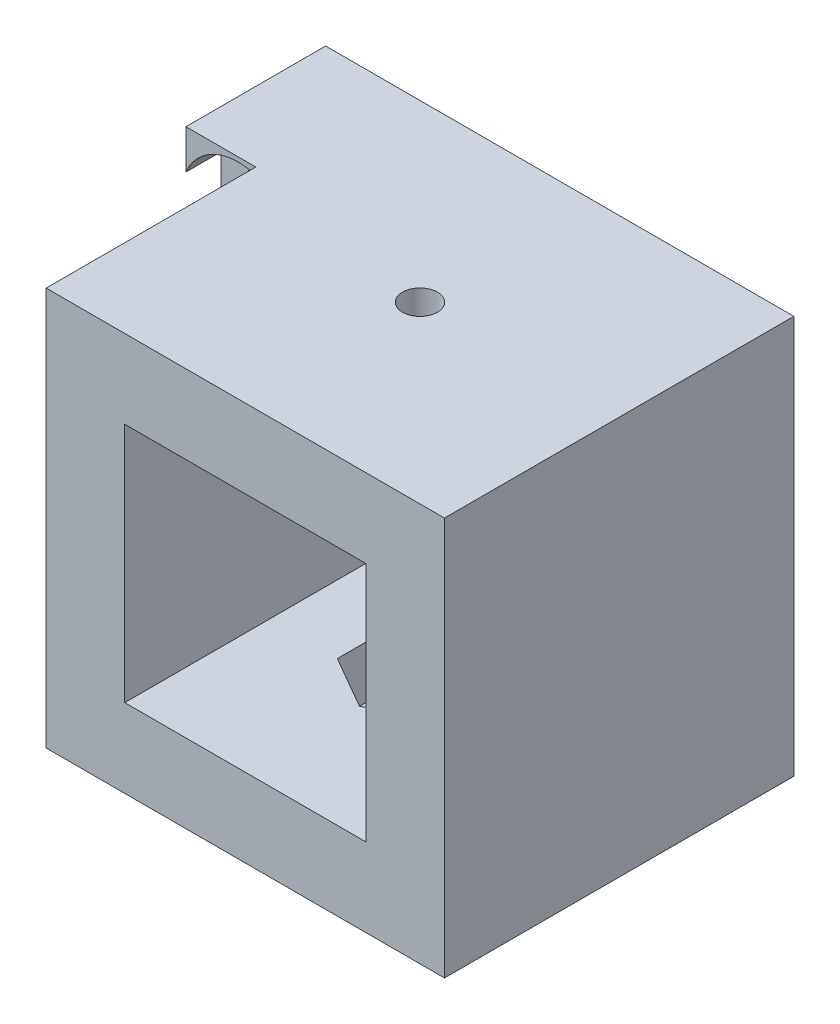
SolidWorks part; units mm, degrees
ref_plane "Alzado" through (0, 0, 0) normal (0, 0, 1) x (1, 0, 0)
ref_plane "Planta" through (0, 0, 0) normal (0, 1, 0) x (1, 0, 0)
ref_plane "Vista lateral" through (0, 0, 0) normal (1, 0, 0) x (0, 0, -1)
sketch "Croquis1" plane through (0, 0, 0) normal (0, 0, 1) x (1, 0, 0)
  line L0 (-11.4, -11.4) -> (-11.4, 11.4)
  line L1 (-6.9, -6.9) -> (6.9, -6.9)
  line L2 (-6.9, -6.9) -> (-6.9, 6.9)
  line L3 (-6.9, 6.9) -> (6.9, 6.9)
  line L4 (6.9, -6.9) -> (6.9, 6.9)
  line L5 (-6.9, -6.9) -> (6.9, 6.9) construction
  line L6 (-6.9, 6.9) -> (6.9, -6.9) construction
  line L7 (-11.4, 11.4) -> (11.4, 11.4)
  line L8 (11.4, -11.4) -> (11.4, 11.4)
  line L9 (-11.4, -11.4) -> (11.4, -11.4)
  point P0 (0, 0)
  dimension "D1" = 13.8
  dimension "D2" = 13.8
  dimension "D3" = 4.5
extrude "Saliente-Extruir1" add sketch "Croquis1" along normal mid plane 20
sketch "Croquis2" plane through (0, -6.9, 0) normal (0, 1, 0) x (1, 0, 0)
  line L1 (3, -1.7321) -> (3, 1.7321)
  line L2 (3, 1.7321) -> (0, 3.4641)
  line L3 (0, 3.4641) -> (-3, 1.7321)
  line L4 (-3, 1.7321) -> (-3, -1.7321)
  line L5 (-3, -1.7321) -> (0, -3.4641)
  line L6 (0, -3.4641) -> (3, -1.7321)
  circle A0 centre (0, 0) radius 3 construction
  dimension "D1" = 6
extrude "Cortar-Extruir1" cut sketch "Croquis2" against normal blind 3
sketch "Croquis3" plane through (0, -9.9, 0) normal (0, 1, 0) x (1, 0, 0)
  circle A0 centre (0, 0) radius 1.75
  dimension "D1" = 3.5
extrude "Cortar-Extruir2" cut sketch "Croquis3" against normal blind 3
sketch "Croquis4" plane through (0, 0, -10) normal (0, 0, -1) x (-1, 0, 0)
  line L0 (12.4, 11.4) -> (12.4, 4.4) construction
  line L1 (11.4, 11.4) -> (15.4, 11.4)
  line L2 (11.4, 11.4) -> (11.4, 4.4)
  line L3 (11.4, 4.4) -> (15.4, 4.4)
  line L4 (-11.4, -11.4) -> (11.4, -11.4)
  line L5 (11.4, -11.4) -> (11.4, 11.4)
  line L6 (11.4, 11.4) -> (-11.4, 11.4)
  line L7 (-11.4, 11.4) -> (-11.4, -11.4)
  line L8 (-11.4, -11.4) -> (11.4, -11.4)
  line L9 (11.4, -11.4) -> (11.4, 11.4)
  line L10 (11.4, 11.4) -> (-11.4, 11.4)
  line L11 (-11.4, 11.4) -> (-11.4, -11.4)
  line L12 (15.4, 11.4) -> (15.4, 4.4)
  circle A0 centre (12.4, 7.9) radius 1.75
  line M12 (11.4, -11.4) -> (11.4, 11.4)
  dimension "D2" = 3.5
  dimension "D3" = 4
  dimension "D4" = 1
  dimension "D5" = 7
  dimension "D1" = 0
extrude "Saliente-Extruir3" add sketch "Croquis4" against normal blind 8 contours L1 L0 A0 L3 L12 | L0 A0 L3 M12 | L0 L1 A0 M12 region at (-13.9, 11.3238, -10) region at (-11.8862, 10.4724, -10) region at (-11.8862, 5.3276, -10)
sketch "Croquis8" plane through (0, 0, -10) normal (0, 0, -1) x (-1, 0, 0)
  circle A0 centre (12.4, 7.9) radius 1.75
extrude "Cortar-Extruir3" cut sketch "Croquis8" against normal blind 4
hole_wizard "Refrentado para tornillo con cabeza plana de M31" positions "Croquis3D2" profile "Croquis9" counterbore size "M3" standard "ISO" end condition through all
sketch3d "Croquis3D2"
  line L0 (-12.4, 7.9, -6) -> (-12.4, 7.9, -10) construction
  point P0 (-12.4, 7.9, -2)
sketch "Croquis9" plane through (-12.4, 7.9, -2) normal (1, 0, 0) x (0, -1, 0)
  line L0 (0, 0) -> (0, 8)
  line L1 (0, 8) -> (1.8, 8)
  line L3 (1.8, 8) -> (1.8, 2)
  line L4 (1.8, 2) -> (3.25, 2)
  line L5 (3.25, 2) -> (3.25, 0)
  line L7 (3.25, 0) -> (0, 0)
  line L11 (0, -6.35) -> (0, 107.95) construction
  dimension "Diámetro de taladro hasta el siguiente" = 3.6
  dimension "Profundidad de taladro hasta el siguiente" = 8
  dimension "Diámetro de refrentado" = 6.5
  dimension "Profundidad de refrentado" = 2
sketch "Croquis11" plane through (0, 0, -2) normal (0, 0, 1) x (1, 0, 0)
  line L0 (-15.4, 9.15) -> (-15.4, 6.65)
  arc A0 (-15.4, 6.65) -> (-15.4, 9.15) centre (-12.4, 7.9) ccw construction
  arc A1 (-15.4, 6.65) -> (-15.4, 9.15) centre (-12.4, 7.9) ccw
extrude "Cortar-Extruir4" cut sketch "Croquis11" along normal blind 7
fillet "Redondeo1" radius 2.2 1 edges at (-15.4, 4.4, -6)
fillet "Redondeo5" radius 3 1 edges at (-11.4, 7.9, 5)
sketch "Croquis12" plane through (0, 11.4, 0) normal (0, 1, 0) x (1, 0, 0)
  circle A0 centre (0, 0) radius 1
  dimension "D1" = 2
extrude "Cortar-Extruir5" cut sketch "Croquis12" against normal blind 10
